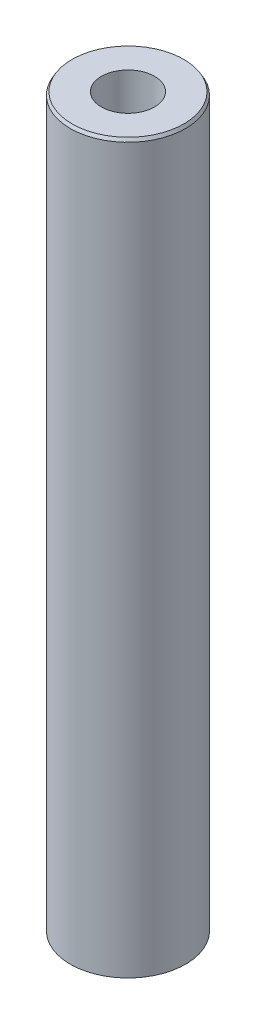
SolidWorks part; units mm, degrees
ref_plane "Front Plane" through (0, 0, 0) normal (0, 0, 1) x (1, 0, 0)
ref_plane "Top Plane" through (0, 0, 0) normal (0, 1, 0) x (1, 0, 0)
ref_plane "Right Plane" through (0, 0, 0) normal (1, 0, 0) x (0, 0, -1)
sketch "Sketch1" plane through (0, 0, 0) normal (0, 1, 0) x (1, 0, 0)
  circle A0 centre (0, 0) radius 47.5
  dimension "SHAFT_OD" = 95
extrude "Boss-Extrude1" add sketch "Sketch1" along normal blind 600
sketch "Sketch2" plane through (0, 0, 0) normal (0, 1, 0) x (1, 0, 0)
  circle A0 centre (0, 0) radius 21.8826
  dimension "BORE_D" = 43.7652
extrude "Cut-Extrude1" cut sketch "Sketch2" along normal through all
chamfer "Chamfer1" distance 2.5465 angle 30 2 edges at (0, 600, 47.5) (0, 0, 47.5) first distance on face at (0, 600, 47.5) first distance on face at (0, 0, 21.8826)
